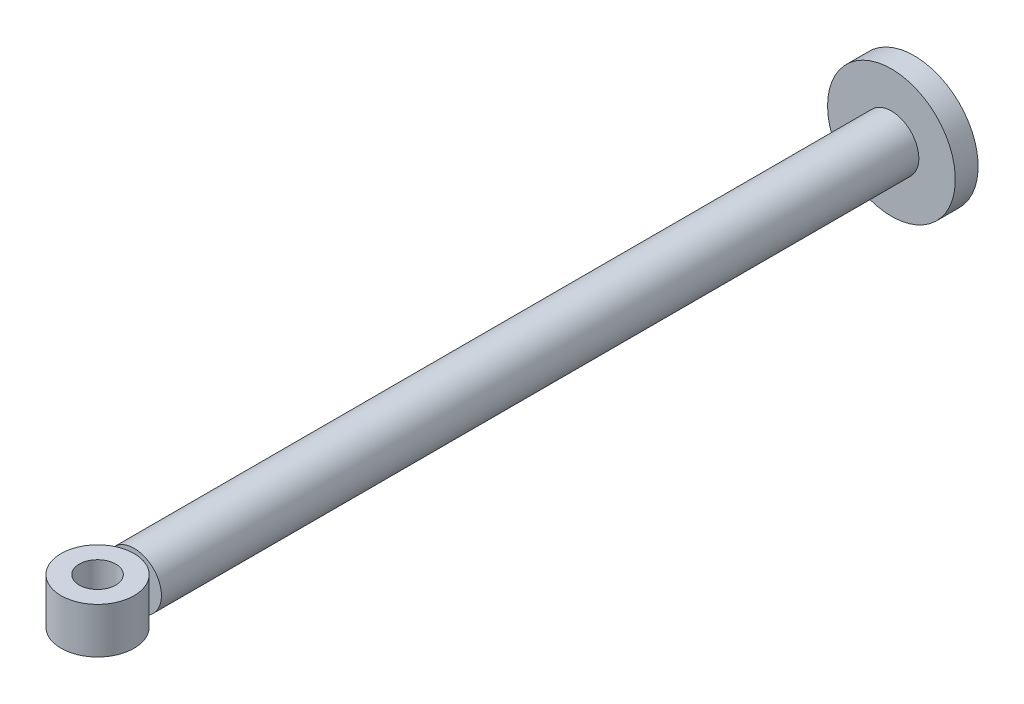
SolidWorks part; units mm, degrees
ref_plane "Front Plane" through (0, 0, 0) normal (0, 0, 1) x (1, 0, 0)
ref_plane "Top Plane" through (0, 0, 0) normal (0, 1, 0) x (1, 0, 0)
ref_plane "Right Plane" through (0, 0, 0) normal (1, 0, 0) x (0, 0, -1)
sketch "Sketch1" plane through (0, 0, 0) normal (0, 0, 1) x (1, 0, 0)
  circle A0 centre (0, 0) radius 3
  dimension "D1" = 6
extrude "Boss-Extrude1" add sketch "Sketch1" along normal blind 85.5
sketch "Sketch2" plane through (0, 0, 0) normal (0, 1, 0) x (1, 0, 0)
  line L0 (0, -85.5) -> (0, -89.5) construction
  line L1 (-3, -85.5) -> (3, -85.5) construction
  circle A0 centre (0, -89.5) radius 2
  circle A1 centre (0, -89.5) radius 4
  dimension "D1" = 8
  dimension "D2" = 4
extrude "Boss-Extrude2" add sketch "Sketch2" along normal blind 2.5 and the other way blind 2.5
sketch "Sketch3" plane through (0, 0, 0) normal (0, 0, -1) x (-1, 0, 0)
  circle A1 centre (0, 0) radius 7
  circle A2 centre (0, 0) radius 3 construction
  dimension "D1" = 4
extrude "Boss-Extrude3" add sketch "Sketch3" against normal blind 2.5
